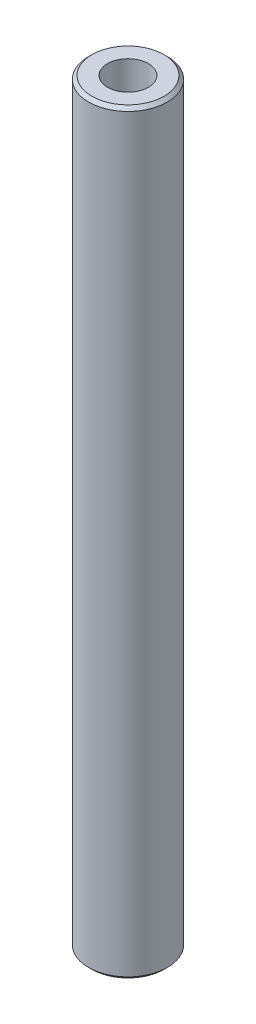
SolidWorks part; units mm, degrees
ref_plane "Front Plane" through (0, 0, 0) normal (0, 0, 1) x (1, 0, 0)
ref_plane "Top Plane" through (0, 0, 0) normal (0, 1, 0) x (1, 0, 0)
ref_plane "Right Plane" through (0, 0, 0) normal (1, 0, 0) x (0, 0, -1)
sketch "Sketch1" plane through (0, 0, 0) normal (0, 1, 0) x (1, 0, 0)
  circle A0 centre (0, 0) radius 5
  dimension "SHAFT_OD" = 10
extrude "Boss-Extrude1" add sketch "Sketch1" along normal blind 95.9293
sketch "Sketch2" plane through (0, 0, 0) normal (0, 1, 0) x (1, 0, 0)
  circle A0 centre (0, 0) radius 2.5994
  dimension "BORE_D" = 5.1989
extrude "Cut-Extrude1" cut sketch "Sketch2" along normal through all
chamfer "Chamfer1" distance 0.4256 angle 45 2 edges at (0, 95.9293, 5) (0, 0, 5)
